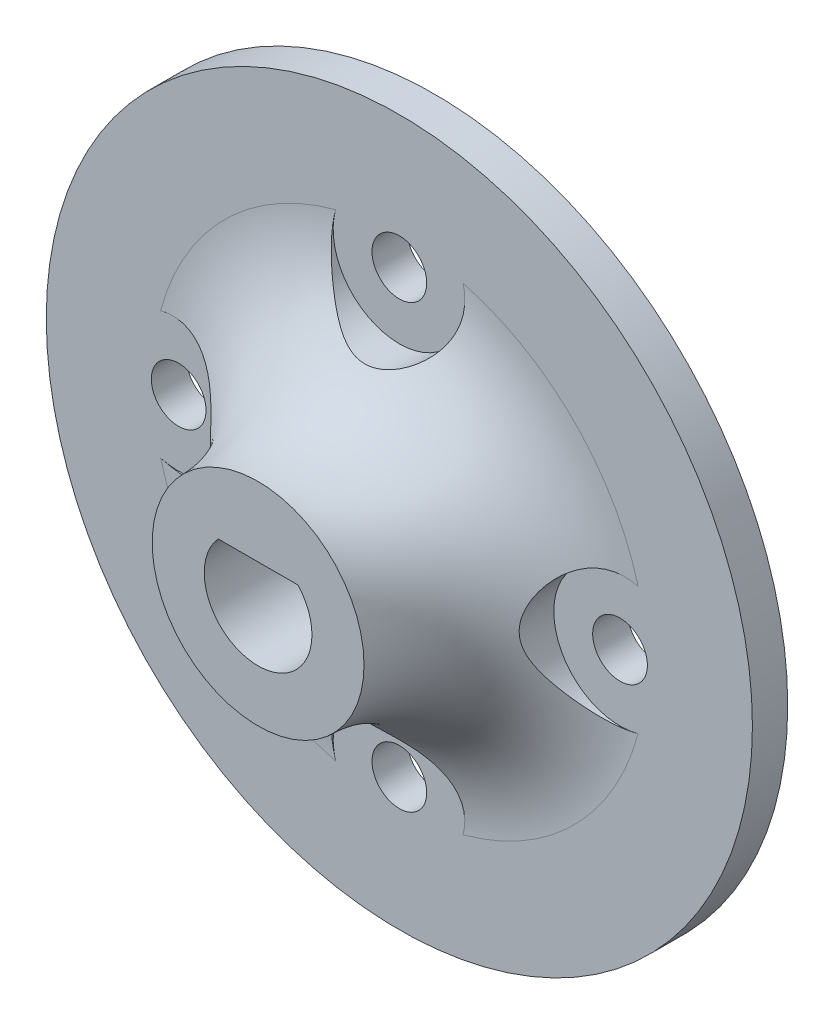
SolidWorks part; units mm, degrees
ref_plane "Plano frontal" through (0, 0, 0) normal (0, 0, 1) x (1, 0, 0)
ref_plane "Plano superior" through (0, 0, 0) normal (0, 1, 0) x (1, 0, 0)
ref_plane "Plano direito" through (0, 0, 0) normal (1, 0, 0) x (0, 0, -1)
sketch "Esboço1" plane through (0, 0, 0) normal (0, 0, 1) x (1, 0, 0)
  circle A0 centre (0, 0) radius 20
  dimension "D1" = 40
extrude "Ressalto-extrusão1" add sketch "Esboço1" along normal blind 2
sketch "Esboço2" plane through (0, 0, 2) normal (0, 0, 1) x (1, 0, 0)
  line L0 (-2.2583, 2.05) -> (2.2583, 2.05)
  line L1 (0, 0) -> (0, 2.05) construction
  arc A0 (-2.2583, 2.05) -> (2.2583, 2.05) centre (0, 0) ccw
  circle A1 centre (0, 0) radius 6
  dimension "D2" = 6.1
  dimension "D3" = 12
  dimension "D1" = 2.05
extrude "Ressalto-extrusão2" add sketch "Esboço2" along normal blind 8
fillet "Filete3" radius 8 1 edges at (6, 0, 2)
sketch "Esboço3" plane through (0, 0, 2) normal (0, 0, 1) x (1, 0, 0)
  line L0 (0, -12.5) -> (0, 0) construction
  circle A0 centre (0, -12.5) radius 1.55
  dimension "D2" = 3.1
  dimension "D1" = 12.5
extrude "Corte-extrusão1" cut sketch "Esboço3" against normal through all contours A0
pattern_circular "PadrãoCircular1" count 4 over 360 about axis through (0, 0, 10) along (0, 0, -1) of "Corte-extrusão1"
sketch "Esboço5" plane through (0, 0, 2) normal (0, 0, 1) x (1, 0, 0)
  circle A1 centre (12.5, 0) radius 3.75
  dimension "D1" = 7.5
extrude "Corte-extrusão2" cut sketch "Esboço5" along normal blind 6
pattern_circular "PadrãoCircular2" count 4 over 360 about axis through (0, 0, 10) along (0, 0, -1) of "Corte-extrusão2"
